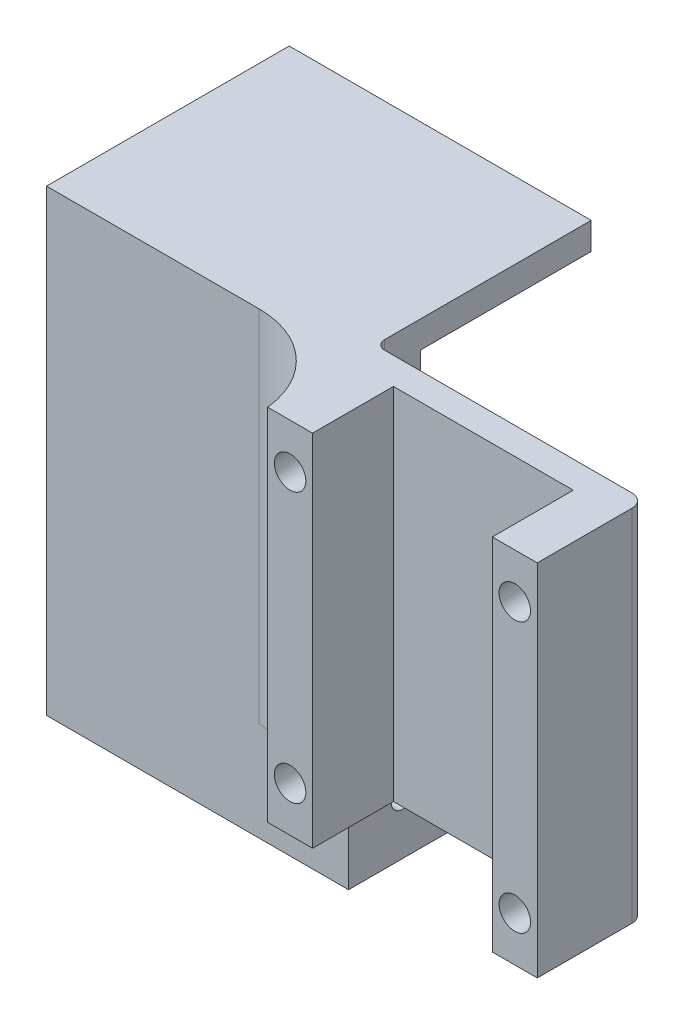
SolidWorks part; units mm, degrees
ref_plane "Plan de face" through (0, 0, 0) normal (0, 0, 1) x (1, 0, 0)
ref_plane "Plan de dessus" through (0, 0, 0) normal (0, 1, 0) x (1, 0, 0)
ref_plane "Plan de droite" through (0, 0, 0) normal (1, 0, 0) x (0, 0, -1)
sketch "Esquisse1" plane through (0, 0, 0) normal (0, 0, 1) x (1, 0, 0)
  line L0 (-15, 20) -> (-15, -20) construction
  line L1 (-4.75, 7.25) -> (4.75, 7.25) construction
  line L2 (-4.75, 7.25) -> (-4.75, -7.25) construction
  line L3 (-4.75, -7.25) -> (4.75, -7.25) construction
  line L4 (4.75, 7.25) -> (4.75, -7.25) construction
  line L5 (-10, 15) -> (10, 15) construction
  line L6 (-10, 15) -> (-10, -15) construction
  line L7 (-10, -15) -> (10, -15) construction
  line L8 (10, 15) -> (10, -15) construction
  line L9 (-15, -20) -> (15, -20)
  line L10 (15, 20) -> (15, -20)
  line L11 (-15, 20) -> (15, 20)
  line L12 (-15, -31) -> (-15, -20)
  line L13 (-48.6, 20) -> (-15, 20)
  line L14 (-48.6, 20) -> (-48.6, -31)
  line L15 (-48.6, -31) -> (-15, -31)
  line L16 (-15, 20) -> (-15, -31) construction
  point P5 (0, 7.25)
  point P7 (-4.75, 0)
  point P14 (-10, 0)
  point P15 (0, 15)
  dimension "D1" = 14.5
  dimension "D2" = 9.5
  dimension "D4" = 20
  dimension "D5" = 30
  dimension "D7" = 51
  dimension "D8" = 33.6
  dimension "D6" = 5
extrude "Boss.-Extru.1" add sketch "Esquisse1" along normal blind 3
sketch "Esquisse3" plane through (0, 0, 0) normal (0, 0, -1) x (-1, 0, 0)
  line L0 (48.6, 20) -> (48.6, -31) construction
  line L1 (15, -31) -> (48.6, -31)
  line L2 (15, -31) -> (15, -28)
  line L3 (15, -28) -> (48.6, -28)
  line L4 (48.6, -31) -> (48.6, -28)
  line L6 (48.6, 20) -> (15, 20)
  line L7 (48.6, 20) -> (48.6, 17)
  line L8 (48.6, 17) -> (15, 17)
  line L9 (15, 20) -> (15, 17)
  dimension "D1" = 3
extrude "Boss.-Extru.2" add sketch "Esquisse3" along normal blind 24
sketch "Esquisse4" plane through (-48.6, 0, 0) normal (-1, 0, 0) x (0, 0, 1)
  line L0 (0, -5.5) -> (-24, -5.5) construction
  line L1 (-24, -28) -> (-19, -28)
  line L2 (-24, -28) -> (-24, -23)
  line L3 (-24, -23) -> (-19, -23)
  line L4 (-19, -28) -> (-19, -23)
  line L5 (0, -28) -> (-5, -28)
  line L6 (0, -28) -> (0, -23)
  line L7 (0, -23) -> (-5, -23)
  line L8 (-5, -28) -> (-5, -23)
  line L9 (0, 17) -> (0, -28) construction
  line L10 (-5, 17) -> (-5, 12)
  line L11 (0, 12) -> (-5, 12)
  line L12 (0, 17) -> (0, 12)
  line L13 (0, 17) -> (-5, 17)
  line L14 (-19, 17) -> (-19, 12)
  line L15 (-24, 12) -> (-19, 12)
  line L16 (-24, 17) -> (-24, 12)
  line L17 (-24, 17) -> (-19, 17)
  line L18 (-12, -5.5) -> (-12, -28) construction
  line L19 (-24, -28) -> (0, -28) construction
  line L20 (-21, -25) -> (-24, -25.5) construction
  line L21 (-21, -25) -> (-21.5, -28) construction
  circle A0 centre (-21, -25) radius 1.25
  circle A1 centre (-3, -25) radius 1.25
  circle A2 centre (-3, 14) radius 1.25
  circle A3 centre (-21, 14) radius 1.25
  line M12 (0, 17) -> (0, -28)
  line M13 (0, -28) -> (-24, -28)
  dimension "D2" = 3
  dimension "D3" = 2.5
  dimension "D1" = 5
extrude "Boss.-Extru.3" add sketch "Esquisse4" against normal blind 2.8
sketch "Esquisse5" plane through (-15, 0, 0) normal (1, 0, 0) x (0, 0, -1)
  line L0 (0, -20) -> (0, 20) construction
  line L1 (5, -23) -> (0, -23)
  line L2 (5, -23) -> (5, -28)
  line L3 (5, -28) -> (0, -28)
  line L4 (0, -23) -> (0, -28)
  line L13 (5, 12) -> (0, 12)
  line L14 (5, 12) -> (5, 17)
  line L15 (5, 17) -> (0, 17)
  line L16 (0, 12) -> (0, 17)
  line L17 (0, 12) -> (0, 17) construction
  line L20 (0, 5.8) -> (5, 5.8)
  line L21 (0, 5.8) -> (0, 0.8)
  line L22 (0, 0.8) -> (5, 0.8)
  line L23 (5, 5.8) -> (5, 0.8)
  circle A0 centre (3, 14) radius 1.25
  circle A1 centre (3, 14) radius 1.25 construction
  circle A3 centre (3, -25) radius 1.25
  circle A5 centre (3, -25) radius 1.25 construction
  circle A8 centre (3, 3.3) radius 1.25
  point P54 (5, 3.3)
  line M11 (0, 17) -> (24, 17)
  dimension "D1" = 10.7
  dimension "D2" = 5
extrude "Boss.-Extru.4" add sketch "Esquisse5" against normal blind 2.8 contours L16 L13 L14 A0 M11 | M11 | L23 L20 L21 L22 A8 | L1 L4 L3 L2 A3 region at (-15, -25.5, -4.9293) region at (-15, 12.0707, -2.5) region at (-15, 5.7293, -2.5)
extrude "Boss.-Extru.5" add sketch "Esquisse4<2>" against normal blind 4.8 contours L4 L3 L2 A0 M13 | L8 L7 A1 M13 M12 region at (-48.6, -25.5, -23.9293) region at (-48.6, -25.5, -4.9293)
sketch "Esquisse4<2>" plane through (-48.6, 0, 0) normal (-1, 0, 0) x (0, 0, 1) same geometry as "Esquisse4"
sketch "Esquisse6" plane through (0, 0, 3) normal (0, 0, 1) x (1, 0, 0)
  line L0 (10, 20) -> (10, -20)
  line L2 (-10, -20) -> (-10, 20)
  line L4 (-15, -20) -> (-15, 20)
  line L5 (-15, 20) -> (15, 20)
  line L6 (15, 20) -> (15, -20)
  line L7 (15, -20) -> (-15, -20)
  line L8 (-10, 0) -> (-15, 0) construction
  line L9 (10, 0) -> (15, 0) construction
  line L10 (-12.5, 15) -> (-12.5, 20) construction
  line L11 (-12.5, 15) -> (-10, 15) construction
  line L12 (-12.5, 15) -> (-15, 15) construction
  line L13 (12.5, 15) -> (10, 15) construction
  circle A1 centre (-12.5, 15) radius 1.75
  circle A2 centre (12.5, 15) radius 1.75
  circle A6 centre (-12.5, -15) radius 1.75
  circle A7 centre (12.5, -15) radius 1.75
  line M5 (15, 20) -> (-48.6, 20)
  line M9 (-15, -20) -> (15, -20)
  line M10 (15, -20) -> (15, 20)
  dimension "D2" = 3.5
  dimension "D1" = 5
extrude "Boss.-Extru.6" add sketch "Esquisse6" along normal blind 9 contours L4 L2 M9 M5 | L0 M5 M9 M10 region at (12.5, 0, 3) region at (-12.5, 0, 3)
fillet "Congé3" radius 10 1 edges at (-15, 0, 3)
fillet "Congé4" radius 1 3 edges at (-15, -20, 1.5) (-15, 3.3, 0) (-15, 16, 0)
fillet "Congé1" radius 1.45 12 edges at (-46.2, -23, -19) (-46.2, -23, -5) (-16.4, 0.8, -5) (-16.4, 5.8, -5) (-16.4, -23, -5) (-16.4, 12, -5) (-16.4, -28, -5) (-46.2, -28, -19) (-46.2, -28, -5) (-47.2, 12, -19) (-47.2, 12, -5) (15, 0, 0)
fillet "Congé2" radius 1 6 edges at (-47.2, 12, -24) (-16.4, -23, 0) (-15.9, 12, 0) (-15.9, 0.8, 0) (-15.9, 5.8, 0) (-46.2, -23, -24)
extrude "Enlèv. mat.-Extru.1" cut sketch "Esquisse6<3>" against normal up to next contours A1 | A6 | A7 | A2 region at (-12.5, 15, 3) region at (-12.5, -15, 3) region at (12.5, -15, 3)
sketch "Esquisse6<3>" plane through (0, 0, 3) normal (0, 0, 1) x (1, 0, 0) same geometry as "Esquisse6"
